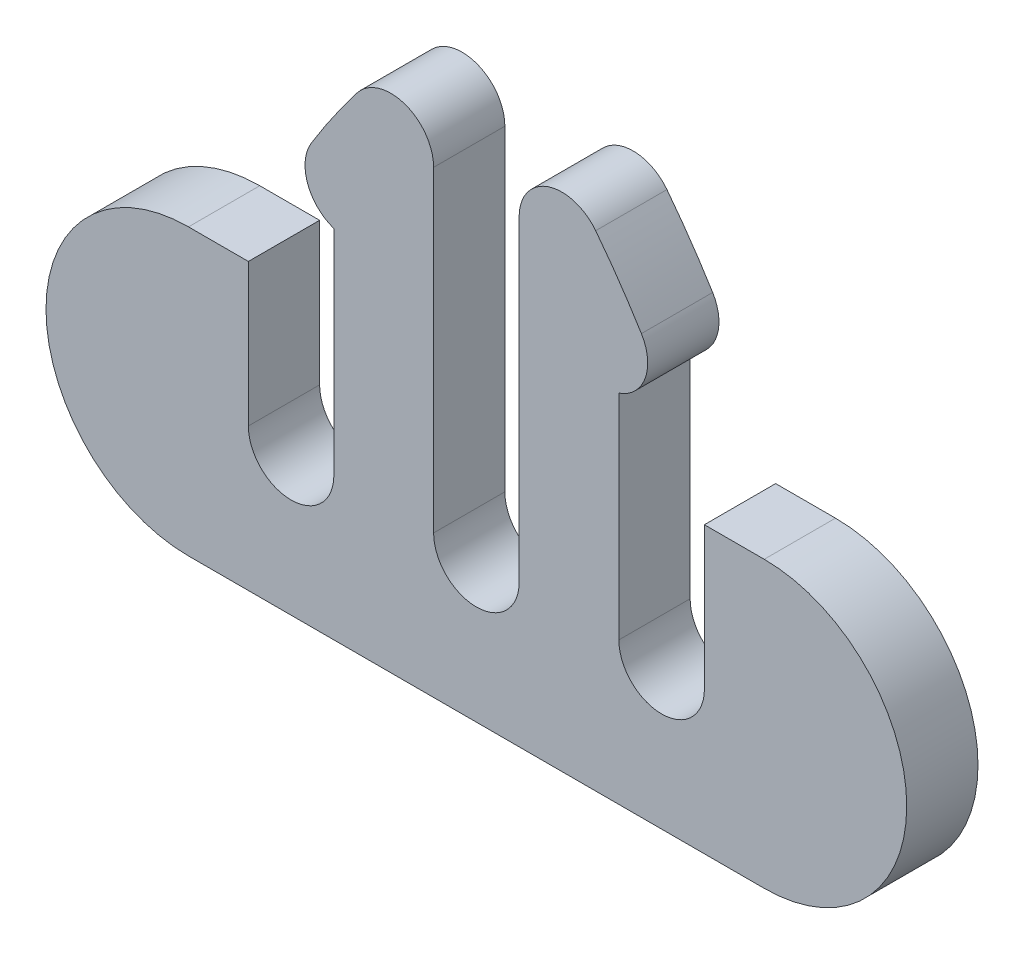
SolidWorks part; units mm, degrees
ref_plane "Front Plane" through (0, 0, 0) normal (0, 0, 1) x (1, 0, 0)
ref_plane "Top Plane" through (0, 0, 0) normal (0, 1, 0) x (1, 0, 0)
ref_plane "Right Plane" through (0, 0, 0) normal (1, 0, 0) x (0, 0, -1)
sketch "Sketch1" plane through (0, 0, 0) normal (0, 0, 1) x (1, 0, 0)
  line L0 (-22.8376, 46.0832) -> (-12.8376, 46.0832) construction
  line L1 (-17.8376, 46.0832) -> (-17.8376, 51.0832) construction
  line L2 (-22.8376, 46.0832) -> (-27.9376, 46.0832)
  line L6 (-22.8376, 46.0832) -> (-22.8376, 48.5832) construction
  line L7 (-22.8376, 46.0832) -> (-22.8376, 48.5832)
  line L8 (-22.8376, 48.5832) -> (-24.8376, 48.5832)
  line L9 (-24.8376, 48.5832) -> (-19.3376, 56.0832) construction
  line L10 (-22.0876, 52.3332) -> (-22.4236, 52.5796) construction
  line L11 (-19.3376, 56.0832) -> (-19.3376, 46.0832)
  line L12 (-13.5876, 52.3332) -> (-13.2516, 52.5796) construction
  line L13 (-10.8376, 48.5832) -> (-16.3376, 56.0832) construction
  line L14 (-12.8376, 46.0832) -> (-12.8376, 48.5832) construction
  line L15 (-16.3376, 56.0832) -> (-16.3376, 46.0832)
  line L16 (-12.8376, 48.5832) -> (-10.8376, 48.5832)
  line L17 (-12.8376, 46.0832) -> (-12.8376, 48.5832)
  line L18 (-12.8376, 46.0832) -> (-7.7376, 46.0832)
  line L19 (-27.9376, 46.0832) -> (-27.9376, 36.0832) construction
  line L20 (-7.7376, 36.0832) -> (-27.9376, 36.0832)
  line L22 (-7.7376, 46.0832) -> (-7.7376, 36.0832) construction
  arc A0 (-19.3376, 46.0832) -> (-16.3376, 46.0832) centre (-17.8376, 46.0832) ccw
  arc A2 (-7.7376, 36.0832) -> (-7.7376, 46.0832) centre (-7.7376, 41.0832) ccw
  arc A3 (-27.9376, 46.0832) -> (-27.9376, 36.0832) centre (-27.9376, 41.0832) ccw
  spline S0 degree 2 poles (-19.3376, 56.0832) (-22.7596, 52.826) (-24.8376, 48.5832) knots 0 0 0 1 1 1
  spline S1 degree 2 poles (-16.3376, 56.0832) (-12.9156, 52.826) (-10.8376, 48.5832) knots 0 0 0 1 1 1
  point P3 (0, 0)
  point P6 (-17.8376, 51.0832)
extrude "Boss-Extrude1" add sketch "Sketch1" along normal blind 2.5
sketch "Sketch2" plane through (0, 0, 2.5) normal (0, 0, 1) x (1, 0, 0)
  line L0 (-12.8376, 46.0832) -> (-11.3376, 46.0832) construction
  line L1 (-7.7376, 46.0832) -> (-12.8376, 46.0832) construction
  line L2 (-11.3376, 46.0832) -> (-11.3376, 41.0832) construction
  line L3 (-9.8376, 46.0832) -> (-9.8376, 41.0832)
  line L4 (-12.8376, 46.0832) -> (-12.8376, 41.0832)
  line L5 (-17.8376, 44.5832) -> (-17.8376, 36.0832) construction
  line L6 (-27.9376, 36.0832) -> (-7.7376, 36.0832) construction
  line L7 (-24.3376, 46.0832) -> (-24.3376, 41.0832) construction
  line L8 (-25.8376, 46.0832) -> (-25.8376, 41.0832)
  line L9 (-22.8376, 46.0832) -> (-22.8376, 41.0832)
  line L10 (-22.8376, 46.0832) -> (-24.3376, 46.0832) construction
  line L11 (-17.8376, 44.5832) -> (-11.3376, 44.5832) construction
  line L12 (-14.5876, 44.5832) -> (-14.5876, 36.0832) construction
  line L13 (-16.3376, 46.0832) -> (-17.8376, 46.0832) construction
  line L14 (-17.8376, 46.0832) -> (-17.8376, 41.0832) construction
  line L15 (-19.3376, 46.0832) -> (-19.3376, 41.0832)
  line L16 (-16.3376, 46.0832) -> (-16.3376, 41.0832)
  arc A0 (-19.3376, 46.0832) -> (-16.3376, 46.0832) centre (-17.8376, 46.0832) ccw construction
  arc A1 (-9.8376, 46.0832) -> (-12.8376, 46.0832) centre (-11.3376, 46.0832) ccw
  arc A2 (-12.8376, 41.0832) -> (-9.8376, 41.0832) centre (-11.3376, 41.0832) ccw
  arc A3 (-25.8376, 46.0832) -> (-22.8376, 46.0832) centre (-24.3376, 46.0832) cw
  arc A4 (-22.8376, 41.0832) -> (-25.8376, 41.0832) centre (-24.3376, 41.0832) cw
  arc A5 (-19.3376, 46.0832) -> (-16.3376, 46.0832) centre (-17.8376, 46.0832) cw
  arc A6 (-16.3376, 41.0832) -> (-19.3376, 41.0832) centre (-17.8376, 41.0832) cw
  point P5 (-11.3376, 43.5832)
  point P20 (-24.3376, 43.5832)
  point P33 (-17.8376, 43.5832)
extrude "Cut-Extrude1" cut sketch "Sketch2" against normal up to surface (2.5 mm away) up to face at (-17.4448, 46.6903, 0)
fillet "Fillet1" radius 1.5 2 edges at (-10.8376, 48.5832, 1.25) (-24.8376, 48.5832, 1.25)
fillet "Fillet2" radius 1.5 2 edges at (-16.3376, 56.0832, 1.25) (-19.3376, 56.0832, 1.25)
